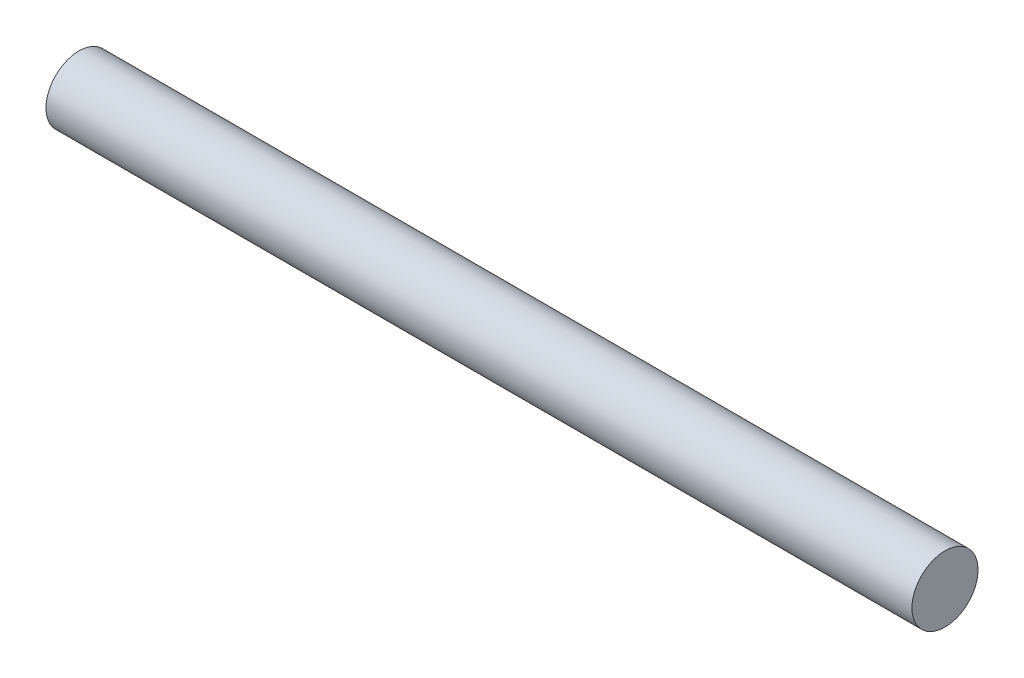
SolidWorks part; units mm, degrees
ref_plane "Front Plane" through (0, 0, 0) normal (0, 0, 1) x (1, 0, 0)
ref_plane "Top Plane" through (0, 0, 0) normal (0, 1, 0) x (1, 0, 0)
ref_plane "Right Plane" through (0, 0, 0) normal (1, 0, 0) x (0, 0, -1)
sketch "Sketch2" plane through (0, 0, 0) normal (1, 0, 0) x (0, 0, -1)
  circle A0 centre (0, 0) radius 1.985
  point P3 (0, 0)
  dimension "D1" = 3.97
extrude "Boss-Extrude1" add sketch "Sketch2" along normal blind 52
